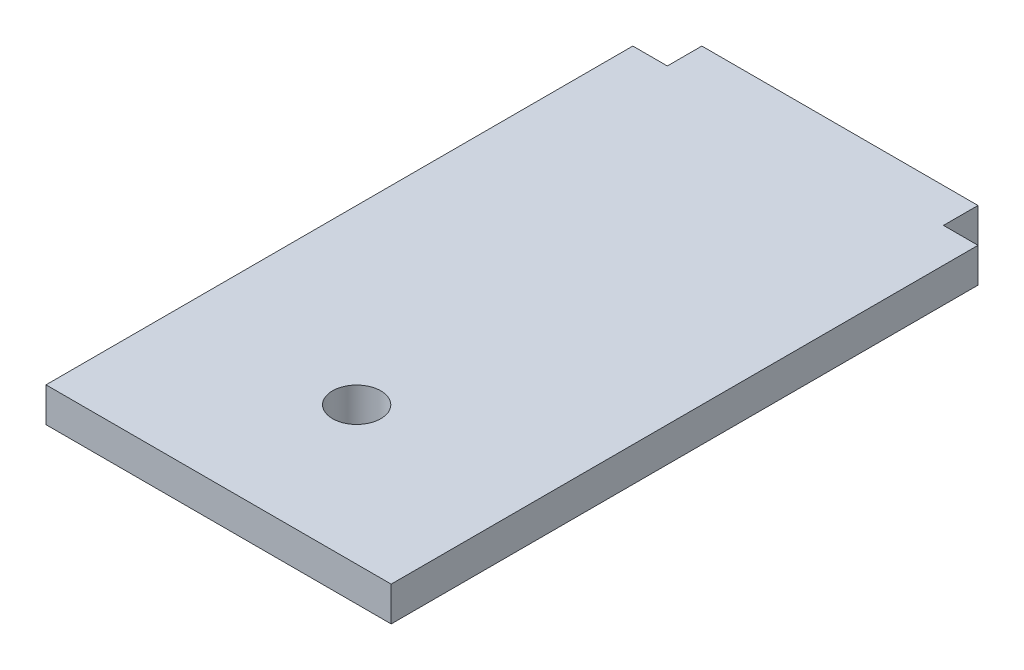
SolidWorks part; units mm, degrees
ref_plane "Front Plane" through (0, 0, 0) normal (0, 0, 1) x (1, 0, 0)
ref_plane "Top Plane" through (0, 0, 0) normal (0, 1, 0) x (1, 0, 0)
ref_plane "Right Plane" through (0, 0, 0) normal (1, 0, 0) x (0, 0, -1)
sketch "Sketch1" plane through (0, 0, 0) normal (0, 1, 0) x (1, 0, 0)
  line L0 (0, 85) -> (5, 85)
  line L1 (0, 0) -> (50, 0)
  line L2 (0, 0) -> (0, 85)
  line L3 (5, 90) -> (45, 90)
  line L4 (50, 0) -> (50, 85)
  line L5 (5, 90) -> (5, 85)
  line L6 (50, 85) -> (45, 85)
  line L7 (45, 85) -> (45, 90)
  line L8 (0, 20) -> (50, 20) construction
  circle A0 centre (25, 20) radius 3.5
  point P10 (25, 0)
  dimension "D6" = 7
  dimension "D1" = 85
  dimension "D2" = 5
  dimension "D3" = 5
  dimension "D4" = 5
  dimension "D5" = 50
  dimension "D7" = 20
extrude "Hammer" add sketch "Sketch1" along normal blind 5
